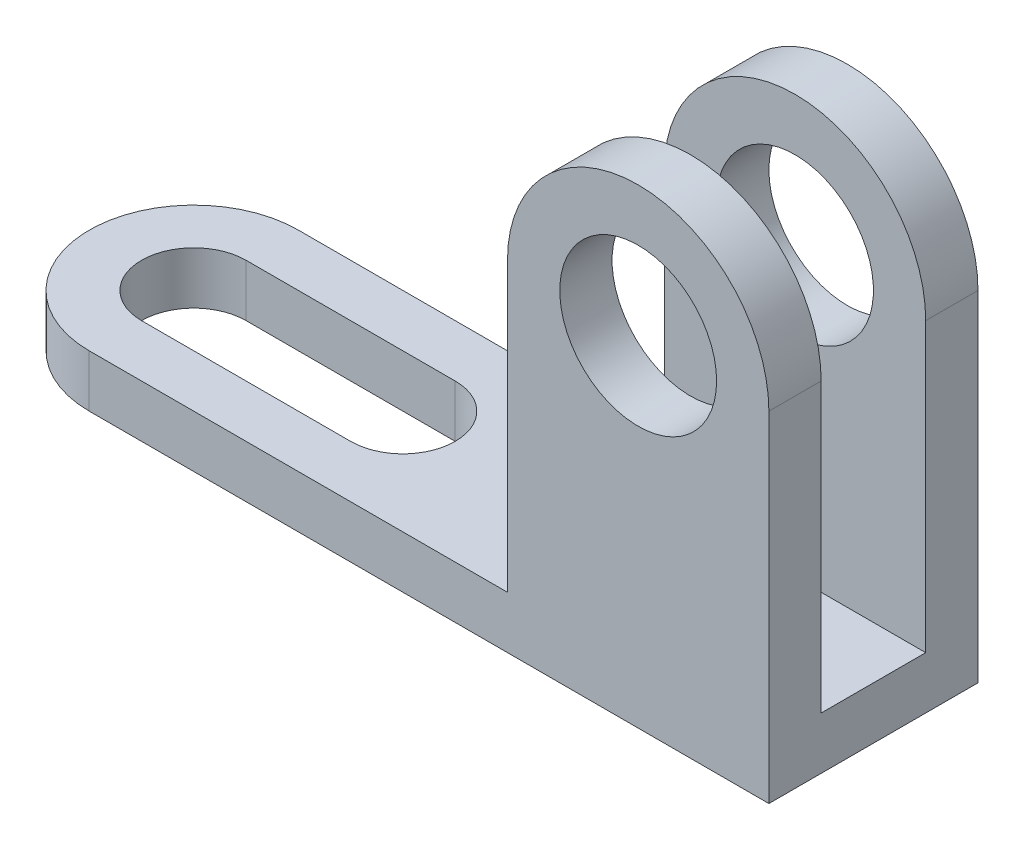
SolidWorks part; units mm, degrees
ref_plane "Front Plane" through (0, 0, 0) normal (0, 0, 1) x (1, 0, 0)
ref_plane "Top Plane" through (0, 0, 0) normal (0, 1, 0) x (1, 0, 0)
ref_plane "Right Plane" through (0, 0, 0) normal (1, 0, 0) x (0, 0, -1)
sketch "Sketch1" plane through (0, 0, 0) normal (0, 1, 0) x (1, 0, 0)
  line L0 (-13.2001, 20) -> (178.6786, 20) construction
  line L1 (20, 0) -> (150, 0)
  line L3 (20, 40) -> (150, 40)
  line L4 (150, 0) -> (150, 40)
  line L5 (20, 67.2255) -> (20, -14.8659) construction
  line L6 (60, 67.2255) -> (60, -14.8659) construction
  line L7 (20, 30) -> (60, 30)
  line L8 (20, 10) -> (60, 10)
  arc A1 (20, 30) -> (20, 10) centre (20, 20) ccw
  arc A2 (60, 10) -> (60, 30) centre (60, 20) ccw
  arc A3 (20, 40) -> (20, 0) centre (20, 20) ccw
  dimension "D5" = 40
  dimension "D4" = 20
extrude "Boss-Extrude1" add sketch "Sketch1" along normal blind 10
sketch "Sketch2" plane through (0, 10, 0) normal (0, 1, 0) x (1, 0, 0)
  line L1 (150, 0) -> (100, 0)
  line L2 (150, 0) -> (150, 10)
  line L3 (150, 10) -> (100, 10)
  line L4 (100, 0) -> (100, 10)
  dimension "D1" = 50
  dimension "D2" = 10
extrude "Boss-Extrude2" add sketch "Sketch2" along normal blind 80
sketch "Sketch3" plane through (0, 0, 0) normal (0, 0, 1) x (1, 0, 0)
  line L0 (125, 104.8534) -> (125, -16.9676) construction
  line L3 (150, 90) -> (150, 0) construction
  line L4 (92.0015, 65) -> (164.2914, 65) construction
  circle A1 centre (125, 65) radius 15
  arc A2 (150, 65) -> (100, 65) centre (125, 65) ccw
  line M4 (150, 0) -> (150, 90)
  line M5 (150, 90) -> (100, 90)
  line M6 (100, 90) -> (100, 10)
  dimension "D2" = 25
extrude "Cut-Extrude2" cut sketch "Sketch3" against normal blind 80 contours A2 M5 M6 | A2 M4 M5 | A1 region at (125, 65, 0) region at (105.5842, 84.4158, 0) region at (144.4158, 84.4158, 0)
sketch "Sketch4" plane through (0, 10, 0) normal (0, 1, 0) x (1, 0, 0)
  line L1 (150, 40) -> (100, 40)
  line L2 (150, 40) -> (150, 30)
  line L3 (150, 30) -> (100, 30)
  line L4 (100, 40) -> (100, 30)
  dimension "D1" = 50
  dimension "D2" = 10
extrude "Boss-Extrude3" add sketch "Sketch4" along normal blind 80
sketch "Sketch5" plane through (0, 0, -40) normal (0, 0, -1) x (-1, 0, 0)
  line L0 (-125, 100.7177) -> (-125, -4.9121) construction
  line L1 (-168.696, 65) -> (-78.2253, 65) construction
  line L2 (-150, 90) -> (-100, 90) construction
  line L3 (-100, 90) -> (-100, 10) construction
  arc A0 (-100, 65) -> (-150, 65) centre (-125, 65) ccw
  circle A1 centre (-125, 65) radius 15
  line M6 (-100, 10) -> (-100, 90)
  line M7 (-100, 90) -> (-150, 90)
  line M8 (-150, 90) -> (-150, 0)
  dimension "D1" = 25
  dimension "D2" = 25
extrude "Cut-Extrude3" cut sketch "Sketch5" against normal blind 80 contours A1 | A0 M7 M8 | A0 M6 M7 region at (144.4158, 84.4158, -40) region at (105.5842, 84.4158, -40) region at (125, 65, -40)
